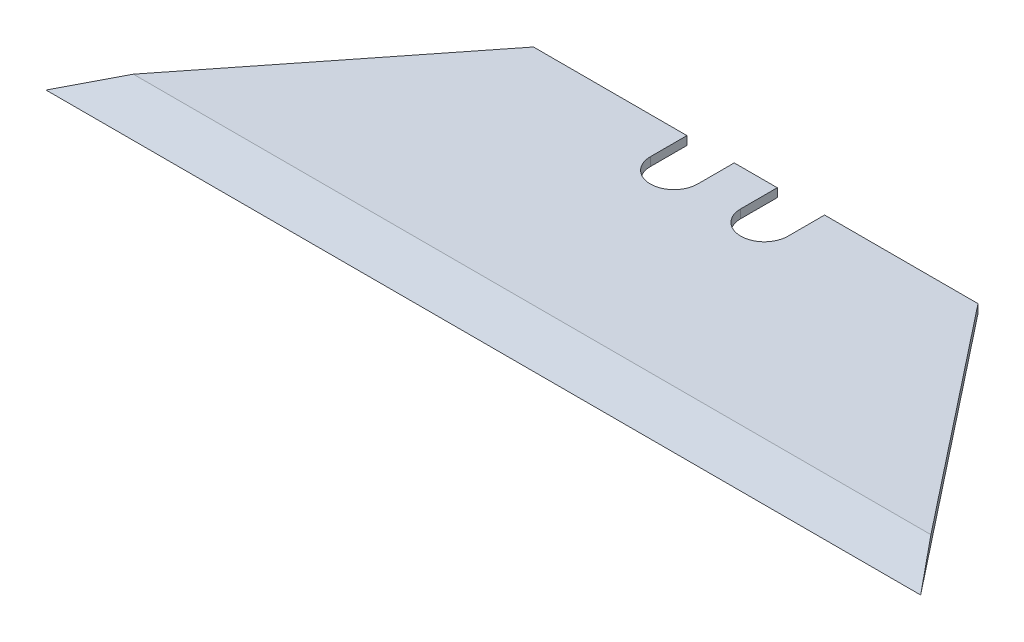
SolidWorks part; units mm, degrees
material "201 Annealed Stainless Steel (SS)"
ref_plane "Front Plane" through (0, 0, 0) normal (0, 0, 1) x (1, 0, 0)
ref_plane "Top Plane" through (0, 0, 0) normal (0, 1, 0) x (1, 0, 0)
ref_plane "Right Plane" through (0, 0, 0) normal (1, 0, 0) x (0, 0, -1)
sketch "Sketch1" plane through (0, 0, 0) normal (0, 1, 0) x (1, 0, 0)
  line L0 (0, 0) -> (61, 0)
  line L1 (61, 0) -> (46, 19)
  line L2 (46, 19) -> (15, 19)
  line L3 (15, 19) -> (0, 0)
  point P3 (30.5, 19)
  point P6 (30.5, 0)
  dimension "D1" = 19
  dimension "D2" = 31
  dimension "D3" = 61
extrude "Boss-Extrude1" add sketch "Sketch1" along normal blind 0.6
chamfer "Chamfer1" distance 0.6 angle 80 1 edges at (30.5, 0.6, 0) first distance on face at (30.5, 0.3, 0)
sketch "Sketch2" plane through (0, 0.6, 0) normal (0, 1, 0) x (1, 0, 0)
  line L0 (27.35, 16.4509) -> (27.35, 22.4872) construction
  line L1 (25.7, 16.4509) -> (25.7, 22.4872)
  line L2 (29, 16.4509) -> (29, 22.4872)
  line L3 (46, 19) -> (15, 19) construction
  line L4 (33.65, 16.4509) -> (33.65, 22.4872) construction
  line L5 (32, 16.4509) -> (32, 22.4872)
  line L6 (35.3, 16.4509) -> (35.3, 22.4872)
  arc A0 (25.7, 16.4509) -> (29, 16.4509) centre (27.35, 16.4509) ccw
  arc A1 (29, 22.4872) -> (25.7, 22.4872) centre (27.35, 22.4872) ccw
  arc A2 (32, 16.4509) -> (35.3, 16.4509) centre (33.65, 16.4509) ccw
  arc A3 (35.3, 22.4872) -> (32, 22.4872) centre (33.65, 22.4872) ccw
  point P2 (27.35, 19.4691)
  point P12 (33.65, 19.4691)
  point P17 (30.5, 19)
  dimension "D1" = 2.5491
  dimension "D2" = 1.5
  dimension "D3" = 3.3
  dimension "D4" = 3
extrude "Cut-Extrude1" cut sketch "Sketch2" against normal through all both and the other way through all
